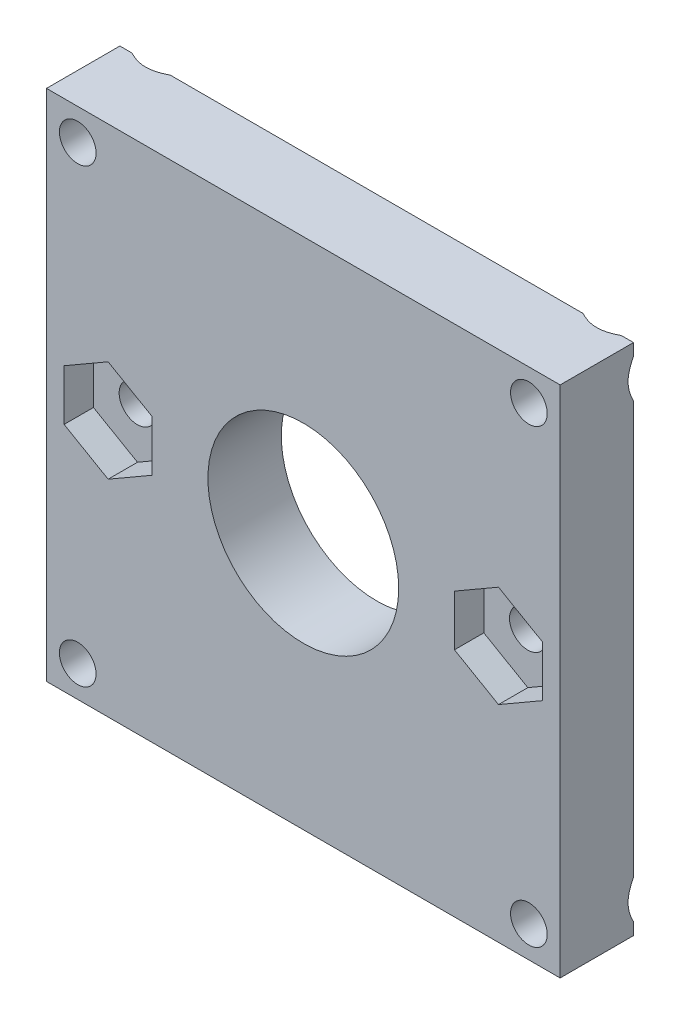
SolidWorks part; units mm, degrees
ref_plane "Alzado" through (0, 0, 0) normal (0, 0, 1) x (1, 0, 0)
ref_plane "Planta" through (0, 0, 0) normal (0, 1, 0) x (1, 0, 0)
ref_plane "Vista lateral" through (0, 0, 0) normal (1, 0, 0) x (0, 0, -1)
sketch "Croquis1" plane through (0, 0, 0) normal (0, 0, 1) x (1, 0, 0)
  line L0 (-17.5, 17.5) -> (-17.5, 13.25) construction
  line L1 (17.5, -17.5) -> (-17.5, -17.5)
  line L2 (17.5, -17.5) -> (17.5, 17.5)
  line L3 (17.5, 17.5) -> (-17.5, 17.5)
  line L4 (-17.5, -17.5) -> (-17.5, 17.5)
  line L5 (17.5, -17.5) -> (-17.5, 17.5) construction
  line L6 (17.5, 17.5) -> (-17.5, -17.5) construction
  line L7 (-17.5, 13.25) -> (-15.37, 13.25) construction
  line L8 (-15.37, 13.25) -> (-15.37, 15.37) construction
  line L9 (17.5, 13.25) -> (15.37, 13.25) construction
  line L10 (15.37, 13.25) -> (15.37, 15.37) construction
  line L11 (15.37, -17.5) -> (15.37, -15.37) construction
  line L12 (-17.5, -15.37) -> (-15.37, -15.37) construction
  line L13 (-13.3, 0) -> (13.3, 0)
  circle A0 centre (-15.37, 15.37) radius 1.25
  circle A1 centre (15.37, 15.37) radius 1.25
  circle A2 centre (15.37, -15.37) radius 1.25
  circle A3 centre (-15.37, -15.37) radius 1.25
  circle A4 centre (0, 0) radius 6.5
  circle A5 centre (13.3, 0) radius 1.25
  circle A6 centre (-13.3, 0) radius 1.25
  point P0 (0, 0)
  point P24 (0, 0)
  dimension "D5" = 2.5
  dimension "D8" = 2.5
  dimension "D10" = 2.5
  dimension "D12" = 2.5
  dimension "D13" = 13
  dimension "D15" = 2.5
  dimension "D16" = 1.25
  dimension "D1" = 35
  dimension "D2" = 4.25
  dimension "D3" = 2.13
  dimension "D4" = 2.12
  dimension "D6" = 2.13
  dimension "D7" = 2.12
  dimension "D9" = 2.13
  dimension "D11" = 2.13
  dimension "D14" = 13.3
extrude "Saliente-Extruir1" add sketch "Croquis1" along normal blind 5 contours L4 L1 L2 L3 A6 A4 A5 A3 A2 A1 A0 region at (0, -17.005, 0)
sketch "Croquis2" plane through (0, 0, 5) normal (0, 0, 1) x (1, 0, 0)
  line L1 (-13.3, 3.4641) -> (-16.3, 1.7321)
  line L2 (-16.3, 1.7321) -> (-16.3, -1.7321)
  line L3 (-16.3, -1.7321) -> (-13.3, -3.4641)
  line L4 (-13.3, -3.4641) -> (-10.3, -1.7321)
  line L5 (-10.3, -1.7321) -> (-10.3, 1.7321)
  line L6 (-10.3, 1.7321) -> (-13.3, 3.4641)
  line L7 (13.3, 3.4641) -> (10.3, 1.7321)
  line L8 (10.3, 1.7321) -> (10.3, -1.7321)
  line L9 (10.3, -1.7321) -> (13.3, -3.4641)
  line L10 (13.3, -3.4641) -> (16.3, -1.7321)
  line L11 (16.3, -1.7321) -> (16.3, 1.7321)
  line L12 (16.3, 1.7321) -> (13.3, 3.4641)
  circle A0 centre (-13.3, 0) radius 3 construction
  circle A1 centre (13.3, 0) radius 3 construction
extrude "Cortar-Extruir1" cut sketch "Croquis2" against normal blind 2
chamfer "Chaflán1" distance 1.25 angle 45 4 edges at (16.62, -15.37, 0) (-14.12, -15.37, 0) (-14.12, 15.37, 0) (16.62, 15.37, 0)
